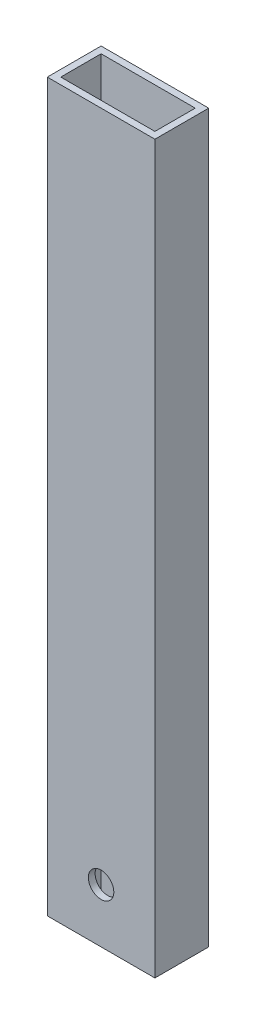
SolidWorks part; units mm, degrees
material "6061-T6 (SS)"
ref_plane "Front Plane" through (0, 0, 0) normal (0, 0, 1) x (1, 0, 0)
ref_plane "Top Plane" through (0, 0, 0) normal (0, 1, 0) x (1, 0, 0)
ref_plane "Right Plane" through (0, 0, 0) normal (1, 0, 0) x (0, 0, -1)
sketch "Sketch2" plane through (0, 0, 0) normal (0, 1, 0) x (1, 0, 0)
  line L1 (-15.1862, -12.028) -> (35.6138, -12.028)
  line L2 (-15.1862, -12.028) -> (-15.1862, 13.372)
  line L3 (-15.1862, 13.372) -> (35.6138, 13.372)
  line L4 (35.6138, -12.028) -> (35.6138, 13.372)
  dimension "D1" = 25.4
  dimension "D2" = 50.8
extrude "Extrude-Thin1" add sketch "Sketch2" along normal blind 355.6 thin thin type one direction reverse wall 3.175
ref_plane "Plane1" through (0, 184.486, -184.486) normal (0, 0.7071, -0.7071) x (-1, 0, 0)
sketch "Sketch8" plane through (0, 184.486, -184.486) normal (0, 0.7071, -0.7071) x (-1, 0, 0)
  line L0 (-35.6138, 241.9918) -> (15.1862, 241.9918) construction
  circle A0 centre (-10.2138, 216.5918) radius 6.35
  point P0 (-10.2138, 216.5918)
  point P3 (-10.2138, 241.9918)
  dimension "D2" = 12.7
  dimension "D1" = 25.4
extrude "Cut-Extrude1" [suppressed] cut sketch "Sketch8" against normal up to surface (63.9513 mm away)
sketch "Sketch9" plane through (-15.1862, 0, 0) normal (-1, 0, 0) x (0, 0, 1)
  line L0 (-13.372, 355.6) -> (12.028, 355.6) construction
  line L1 (-13.372, 355.6) -> (-13.372, 0) construction
  line L2 (2.503, 355.6) -> (-0.672, 520.7) construction
  line L4 (-16.547, 355.6) -> (-3.847, 355.6)
  line L6 (2.503, 355.6) -> (21.553, 355.6)
  line L7 (2.503, 355.6) -> (-3.847, 355.6)
  arc A4 (21.553, 355.6) -> (-16.547, 355.6) centre (2.503, 355.6) ccw
  dimension "D1" = 0
  dimension "D2" = 15.875
extrude "Boss-Extrude5" [suppressed] add sketch "Sketch9" against normal up to surface (3.175 mm away)
sketch "Sketch10" plane through (35.6138, 0, 0) normal (1, 0, 0) x (0, 0, -1)
  line L0 (-12.028, 508) -> (13.372, 508)
  line L12 (13.372, 508) -> (16.547, 508)
  line L13 (-15.203, 508) -> (-12.028, 508)
  arc A2 (16.547, 508) -> (-15.203, 508) centre (0.672, 508) ccw
extrude "Boss-Extrude6" [suppressed] add sketch "Sketch10" against normal up to surface (3.175 mm away)
sketch "Sketch11" [suppressed] plane through (-18.3612, 0, 0) normal (-1, 0, 0) x (0, 0, 1)
  circle A0 centre (-0.672, 508) radius 3.175
  arc A1 (15.203, 508) -> (-16.547, 508) centre (-0.672, 508) ccw construction
  point P6 (-0.672, 523.875)
  dimension "D1" = 6.35
extrude "Cut-Extrude2" [suppressed] cut sketch "Sketch11" against normal up to surface (82.55 mm away)
sketch "Sketch13" plane through (0, 0, 12.028) normal (0, 0, 1) x (1, 0, 0)
  line L0 (-15.1862, 355.6) -> (35.6138, 355.6) construction
  line L1 (-15.1862, 355.6) -> (35.6138, 355.6) construction
  line L3 (35.6138, 355.6) -> (-15.1862, 355.6)
  arc A0 (26.0888, 355.6) -> (-5.6612, 355.6) centre (10.2138, 355.6) ccw construction
  arc A1 (35.6138, 355.6) -> (-15.1862, 355.6) centre (10.2138, 343.2175) ccw
  point P2 (10.2138, 355.6)
  point P7 (35.6138, 355.6)
  point P8 (-15.1862, 355.6)
  point P9 (10.2138, 371.475)
  dimension "D1" = 50.8
  dimension "D2" = 15.875
sketch "Sketch14" plane through (0, 355.6, 0) normal (0, 1, 0) x (1, 0, 0)
  line L1 (32.4388, -8.853) -> (-12.0112, -8.853)
  line L2 (32.4388, -8.853) -> (32.4388, 10.197)
  line L3 (32.4388, 10.197) -> (-12.0112, 10.197)
  line L4 (-12.0112, -8.853) -> (-12.0112, 10.197)
extrude "Extrude-Thin2" [suppressed] add sketch "Sketch14" along normal blind 152.4 thin thin type one direction wall 3.175
sketch "Sketch15" plane through (0, 0, 12.028) normal (0, 0, 1) x (1, 0, 0)
  line L2 (-5.6612, 508) -> (26.0888, 508)
  line L3 (35.6138, 355.6) -> (-15.1862, 355.6) construction
  arc A1 (26.0888, 508) -> (-5.6612, 508) centre (10.2138, 508) ccw
  dimension "D1" = 31.75
  dimension "D2" = 152.4
extrude "Boss-Extrude7" [suppressed] add sketch "Sketch15" along normal blind 3.175 from offset 22.225
sketch "Sketch17" [suppressed] plane through (0, 0, 15.203) normal (0, 0, 1) x (1, 0, 0)
  line L0 (38.7888, 660.4) -> (38.7888, 584.2)
  line L1 (38.7888, 584.2) -> (38.7888, 508) construction
  line L2 (7.0388, 660.4) -> (7.0388, 584.2)
  line L3 (64.1888, 508) -> (64.1888, 660.4)
  line L4 (64.1888, 660.4) -> (38.7888, 660.4)
  line L5 (-18.3612, 508) -> (-18.3612, 660.4)
  line L6 (-18.3612, 660.4) -> (7.0388, 660.4)
  arc A0 (38.7888, 584.2) -> (64.1888, 508) centre (165.7888, 584.2) ccw
  arc A1 (7.0388, 584.2) -> (-18.3612, 508) centre (-119.9612, 584.2) cw
  dimension "D1" = 76.2
sketch "Sketch18" [suppressed] plane through (0, 0, 40.603) normal (0, 0, 1) x (1, 0, 0)
  line L0 (64.1888, 508) -> (-18.3612, 508) construction
  line L1 (64.1888, 508) -> (-18.3612, 508) construction
  line L2 (38.7888, 660.4) -> (64.1888, 508)
  line L3 (7.0388, 660.4) -> (38.7888, 660.4) construction
  line L4 (7.0388, 660.4) -> (-18.3612, 508)
  line L5 (7.0388, 660.4) -> (38.7888, 660.4)
  line L6 (64.1888, 508) -> (64.1888, 482.6)
  line L7 (64.1888, 482.6) -> (-18.3612, 482.6)
  line L8 (-18.3612, 482.6) -> (-18.3612, 508)
  arc A0 (38.7888, 660.4) -> (7.0388, 660.4) centre (22.9138, 660.4) ccw construction
  dimension "D1" = 25.4
extrude "Boss-Extrude9" [suppressed] add sketch "Sketch18" against normal blind 3.175
sketch "Sketch19" [suppressed] plane through (0, 0, 37.428) normal (0, 0, -1) x (-1, 0, 0)
  line L0 (-64.1888, 508) -> (18.3612, 508)
  line L1 (-64.1888, 508) -> (-64.1888, 482.6)
  line L2 (18.3612, 508) -> (18.3612, 482.6)
  line L3 (-64.1888, 482.6) -> (18.3612, 482.6)
  line L4 (15.1862, 508) -> (-61.0138, 508) construction
  dimension "D1" = 25.4
  dimension "D2" = 82.55
extrude "Boss-Extrude10" [suppressed] add sketch "Sketch19" along normal up to next
sketch "Sketch21" [suppressed] plane through (0, 0, -16.547) normal (0, 0, -1) x (-1, 0, 0)
  line L5 (18.3612, 508) -> (-7.0388, 660.4)
  line L6 (18.3612, 482.6) -> (18.3612, 508)
  line L7 (-64.1888, 482.6) -> (18.3612, 482.6)
  line L8 (-64.1888, 508) -> (-64.1888, 482.6)
  line L9 (-38.7888, 660.4) -> (-64.1888, 508)
  line L10 (18.3612, 508) -> (-7.0388, 660.4)
  line L11 (18.3612, 482.6) -> (18.3612, 508)
  line L12 (-64.1888, 482.6) -> (18.3612, 482.6)
  line L13 (-64.1888, 508) -> (-64.1888, 482.6)
  line L14 (-38.7888, 660.4) -> (-64.1888, 508)
  arc A1 (-7.0388, 660.4) -> (-38.7888, 660.4) centre (-22.9138, 660.4) ccw
  arc A2 (-7.0388, 660.4) -> (-38.7888, 660.4) centre (-22.9138, 660.4) ccw
  dimension "D1" = 0
extrude "Boss-Extrude12" [suppressed] add sketch "Sketch21" along normal blind 3.175 from offset 22.225 separate body
sketch "Sketch22" [suppressed] plane through (0, 0, -38.772) normal (0, 0, 1) x (1, 0, 0)
  line L1 (64.1888, 482.6) -> (-18.3612, 482.6)
  line L2 (64.1888, 482.6) -> (64.1888, 508)
  line L3 (64.1888, 508) -> (-18.3612, 508)
  line L4 (-18.3612, 482.6) -> (-18.3612, 508)
extrude "Boss-Extrude13" [suppressed] add sketch "Sketch22" along normal up to surface (22.225 mm away)
sketch "Sketch16" [suppressed] plane through (0, 0, 15.203) normal (0, 0, 1) x (1, 0, 0)
  arc A0 (38.7888, 660.4) -> (7.0388, 660.4) centre (22.9138, 660.4) ccw construction
  arc A1 (38.7888, 660.4) -> (7.0388, 660.4) centre (22.9138, 660.4) ccw construction
  circle A2 centre (22.9138, 660.4) radius 3.175
  dimension "D1" = 6.35
extrude "Cut-Extrude6" [suppressed] cut sketch "Sketch16" against normal through all both and the other way through all
sketch "Sketch23" plane through (0, 355.6, 0) normal (0, 1, 0) x (1, 0, 0)
  line L1 (91.5301, -40.8812) -> (-34.4515, -40.8812)
  line L2 (91.5301, -40.8812) -> (91.5301, 37.0604)
  line L3 (91.5301, 37.0604) -> (-34.4515, 37.0604)
  line L4 (-34.4515, -40.8812) -> (-34.4515, 37.0604)
sketch "Sketch25" plane through (0, 0, 0) normal (0, -1, 0) x (1, 0, 0)
  line L0 (-12.0112, -10.197) -> (-12.0112, 8.853) construction
  line L1 (32.4388, -10.197) -> (-12.0112, -10.197) construction
  line L2 (-12.0112, 8.853) -> (32.4388, 8.853) construction
  line L3 (32.4388, 8.853) -> (32.4388, -10.197) construction
  line L4 (-15.1862, 12.028) -> (-15.1862, -13.372)
  line L5 (-15.1862, -13.372) -> (35.6138, -13.372)
  line L6 (35.6138, -13.372) -> (35.6138, 12.028)
  line L7 (35.6138, 12.028) -> (-15.1862, 12.028)
  line L8 (-15.1862, 12.028) -> (-15.1862, -13.372)
  line L9 (-15.1862, -13.372) -> (35.6138, -13.372)
  line L10 (35.6138, -13.372) -> (35.6138, 12.028)
  line L11 (35.6138, 12.028) -> (-15.1862, 12.028)
  line L12 (-12.0112, -10.197) -> (-12.0112, 8.853)
  line L13 (32.4388, -10.197) -> (-12.0112, -10.197)
  line L14 (-12.0112, 8.853) -> (32.4388, 8.853)
  line L15 (32.4388, 8.853) -> (32.4388, -10.197)
  dimension "D1" = 0
extrude "Boss-Extrude14" add sketch "Sketch25" along normal blind 25.4
sketch "Sketch28" plane through (0, 0, -13.372) normal (0, 0, -1) x (-1, 0, 0)
  line L1 (-35.6138, 355.6) -> (-35.6138, -25.4) construction
  line L2 (15.1862, -25.4) -> (-35.6138, -25.4) construction
  circle A0 centre (-10.2138, 0) radius 6
  dimension "D1" = 12
  dimension "D3" = 25.4
  dimension "D2" = 25.4
extrude "Cut-Extrude9" cut sketch "Sketch28" against normal up to surface (25.4 mm away)
sketch "Sketch29" [suppressed] plane through (0, 355.6, 0) normal (0, 1, 0) x (1, 0, 0)
  line L0 (-12.0112, 10.197) -> (-12.0112, -8.853) construction
  line L1 (-12.0112, -8.853) -> (32.4388, -8.853) construction
  line L2 (32.4388, 10.197) -> (-12.0112, 10.197) construction
  line L3 (32.4388, -8.853) -> (32.4388, 10.197) construction
  line L4 (-15.1862, 13.372) -> (-15.1862, -12.028)
  line L5 (-15.1862, -12.028) -> (35.6138, -12.028)
  line L6 (35.6138, -12.028) -> (35.6138, 13.372)
  line L7 (35.6138, 13.372) -> (-15.1862, 13.372)
  line L8 (-15.1862, 13.372) -> (-15.1862, -12.028)
  line L9 (-15.1862, -12.028) -> (35.6138, -12.028)
  line L10 (35.6138, -12.028) -> (35.6138, 13.372)
  line L11 (35.6138, 13.372) -> (-15.1862, 13.372)
  line L12 (-12.0112, 10.197) -> (-12.0112, -8.853)
  line L13 (-12.0112, -8.853) -> (32.4388, -8.853)
  line L14 (32.4388, 10.197) -> (-12.0112, 10.197)
  line L15 (32.4388, -8.853) -> (32.4388, 10.197)
  dimension "D1" = 0
extrude "Cut-Extrude10" [suppressed] cut sketch "Sketch29" against normal blind 203.2
sketch "Sketch30" plane through (0, 355.6, 0) normal (0, 1, 0) x (1, 0, 0)
  line L4 (-15.1862, 13.372) -> (-15.1862, -12.028)
  line L5 (-15.1862, -12.028) -> (35.6138, -12.028)
  line L6 (35.6138, -12.028) -> (35.6138, 13.372)
  line L7 (35.6138, 13.372) -> (-15.1862, 13.372)
  line L8 (-15.1862, 13.372) -> (-15.1862, -12.028)
  line L9 (-15.1862, -12.028) -> (35.6138, -12.028)
  line L10 (35.6138, -12.028) -> (35.6138, 13.372)
  line L11 (35.6138, 13.372) -> (-15.1862, 13.372)
  dimension "D1" = 0
extrude "Cut-Extrude11" cut sketch "Sketch30" against normal blind 38.1
equation "\"0.625n\"=0.5"
